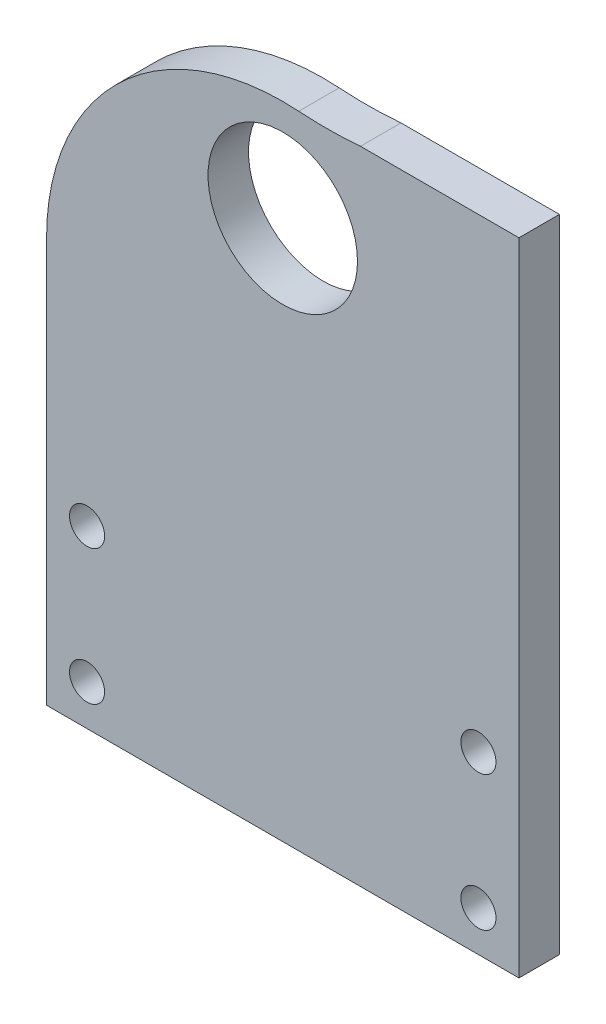
SolidWorks part; units mm, degrees
ref_plane "Ön Düzlem" through (0, 0, 0) normal (0, 0, 1) x (1, 0, 0)
ref_plane "Üst Düzlem" through (0, 0, 0) normal (0, 1, 0) x (1, 0, 0)
ref_plane "Sağ Düzlem" through (0, 0, 0) normal (1, 0, 0) x (0, 0, -1)
sketch "Çizim1" plane through (0, 0, 0) normal (0, 0, 1) x (1, 0, 0)
  line L0 (-21.4104, 4.6521) -> (-21.4104, -5.3479) construction
  line L2 (-56.4104, 29.6521) -> (-56.4104, -30.3479)
  line L3 (-56.4104, -30.3479) -> (13.5896, -30.3479)
  line L4 (13.5896, 29.6521) -> (13.5896, -30.3479)
  line L5 (-12.4104, 4.6521) -> (-12.4104, -5.3479)
  line L6 (-30.4104, 4.6521) -> (-30.4104, -5.3479)
  line L7 (-35.9104, 4.6521) -> (-35.9104, -5.3479) construction
  line L8 (-33.8104, 4.6521) -> (-33.8104, -5.3479)
  line L9 (-38.0104, 4.6521) -> (-38.0104, -5.3479)
  line L10 (-6.9104, 4.6521) -> (-6.9104, -5.3479) construction
  line L11 (-4.8104, 4.6521) -> (-4.8104, -5.3479)
  line L12 (-9.0104, 4.6521) -> (-9.0104, -5.3479)
  circle A0 centre (-21.4104, 49.6521) radius 11.075
  circle A1 centre (-50.4104, -24.3479) radius 2.6
  circle A2 centre (7.5896, -24.3479) radius 2.6
  circle A3 centre (-50.4104, -4.3479) radius 2.6
  circle A4 centre (7.5896, -4.3479) radius 2.6
  arc A5 (-12.4104, 4.6521) -> (-30.4104, 4.6521) centre (-21.4104, 4.6521) ccw
  arc A6 (-30.4104, -5.3479) -> (-12.4104, -5.3479) centre (-21.4104, -5.3479) ccw
  arc A7 (-33.8104, 4.6521) -> (-38.0104, 4.6521) centre (-35.9104, 4.6521) ccw
  arc A8 (-38.0104, -5.3479) -> (-33.8104, -5.3479) centre (-35.9104, -5.3479) ccw
  arc A9 (-4.8104, 4.6521) -> (-9.0104, 4.6521) centre (-6.9104, 4.6521) ccw
  arc A10 (-9.0104, -5.3479) -> (-4.8104, -5.3479) centre (-6.9104, -5.3479) ccw
  arc A13 (13.5896, 29.6521) -> (-56.4104, 29.6521) centre (-21.4104, 29.6521) ccw
  point P16 (-21.4104, -0.3479)
  point P23 (-35.9104, -0.3479)
  point P28 (-6.9104, -0.3479)
  point P37 (23.5896, 59.6521)
  point P40 (-56.4104, 59.6521)
  dimension "D1" = 22.15
  dimension "D5" = 5.2
  dimension "D7" = 5.2
  dimension "D11" = 35
  dimension "D13" = 9
  dimension "D16" = 2.1
  dimension "D17" = 2.1
  dimension "D2" = 80
  dimension "D3" = 70
  dimension "D4" = 6
  dimension "D6" = 6
  dimension "D8" = 6
  dimension "D9" = 6
  dimension "D14" = 14.5
  dimension "D15" = 14.5
  dimension "D18" = 0
  dimension "D19" = 0
  dimension "D20" = 0
  dimension "D21" = 10
  dimension "D22" = 10
  dimension "D23" = 30
  dimension "D10" = 2
extrude "Yükseklik-Ekstrüzyon1" add sketch "Çizim1" along normal blind 6
sketch "Çizim2" plane through (0, 0, 0) normal (0, 0, -1) x (-1, 0, 0)
  line L1 (0, 18.1964) -> (40.1769, 18.1964)
  line L2 (0, 18.1964) -> (0, -14.7426)
  line L3 (0, -14.7426) -> (40.1769, -14.7426)
  line L4 (40.1769, 18.1964) -> (40.1769, -14.7426)
extrude "Yükseklik-Ekstrüzyon2" add sketch "Çizim2" against normal up to surface (6 mm away) up to face at (-47.8104, -4.3479, 6)
sketch "Çizim3" plane through (0, 0, 0) normal (0, 0, -1) x (-1, 0, 0)
  line L1 (-13.5896, 29.6521) -> (9.8927, 29.6521)
  line L2 (-13.5896, 29.6521) -> (-13.5896, 64.6521)
  line L3 (-13.5896, 64.6521) -> (9.8927, 64.6521)
  line L4 (9.8927, 29.6521) -> (9.8927, 64.6521)
extrude "Yükseklik-Ekstrüzyon3" add sketch "Çizim3" against normal up to surface (6 mm away) up to face at (-47.8104, -4.3479, 6)
fillet "Radyus1" radius 60 1 edges at (-9.8927, 62.7028, 3)
